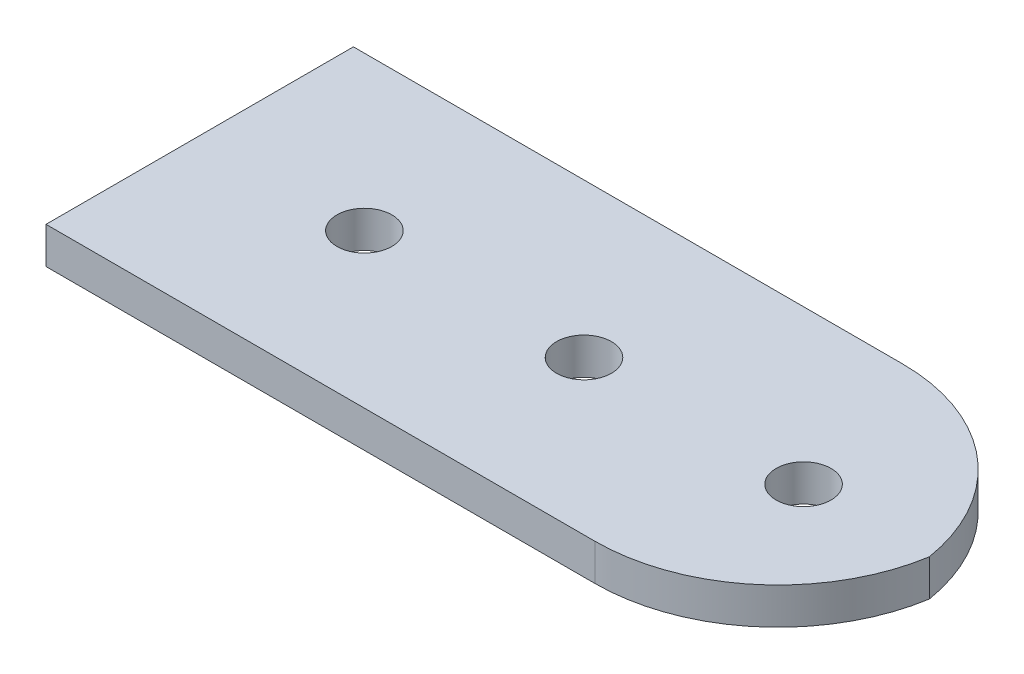
SolidWorks part; units mm, degrees
ref_plane "Front Plane" through (0, 0, 0) normal (0, 0, 1) x (1, 0, 0)
ref_plane "Top Plane" through (0, 0, 0) normal (0, 1, 0) x (1, 0, 0)
ref_plane "Right Plane" through (0, 0, 0) normal (1, 0, 0) x (0, 0, -1)
sketch "Sketch1" plane through (0, 0, 0) normal (0, 1, 0) x (1, 0, 0)
  line L0 (-20, 0) -> (-11, 0)
  line L1 (-20, -8.4) -> (20, -8.4)
  line L2 (-20, -8.4) -> (-20, 8.4)
  line L3 (-20, 8.4) -> (20, 8.4)
  line L4 (20, -8.4) -> (20, 8.4)
  line L5 (-20, -8.4) -> (20, 8.4) construction
  line L6 (-20, 8.4) -> (20, -8.4) construction
  line L7 (-11, 0) -> (1, 0)
  line L8 (1, 0) -> (13, 0)
  circle A0 centre (-11, 0) radius 1.5
  circle A1 centre (1, 0) radius 1.5
  circle A2 centre (13, 0) radius 1.5
  point P0 (0, 0)
  dimension "D1" = 40
  dimension "D2" = 16.8
  dimension "D3" = 9
  dimension "D4" = 12
  dimension "D5" = 12
extrude "Boss-Extrude1" add sketch "Sketch1" along normal blind 2 contours A2 A1 A0 L2 L1 L4 L3 region at (-19.5662, 0, -4.2)
fillet "Fillet1" radius 10 2 edges at (20, 1, -8.4) (20, 1, 8.4)
